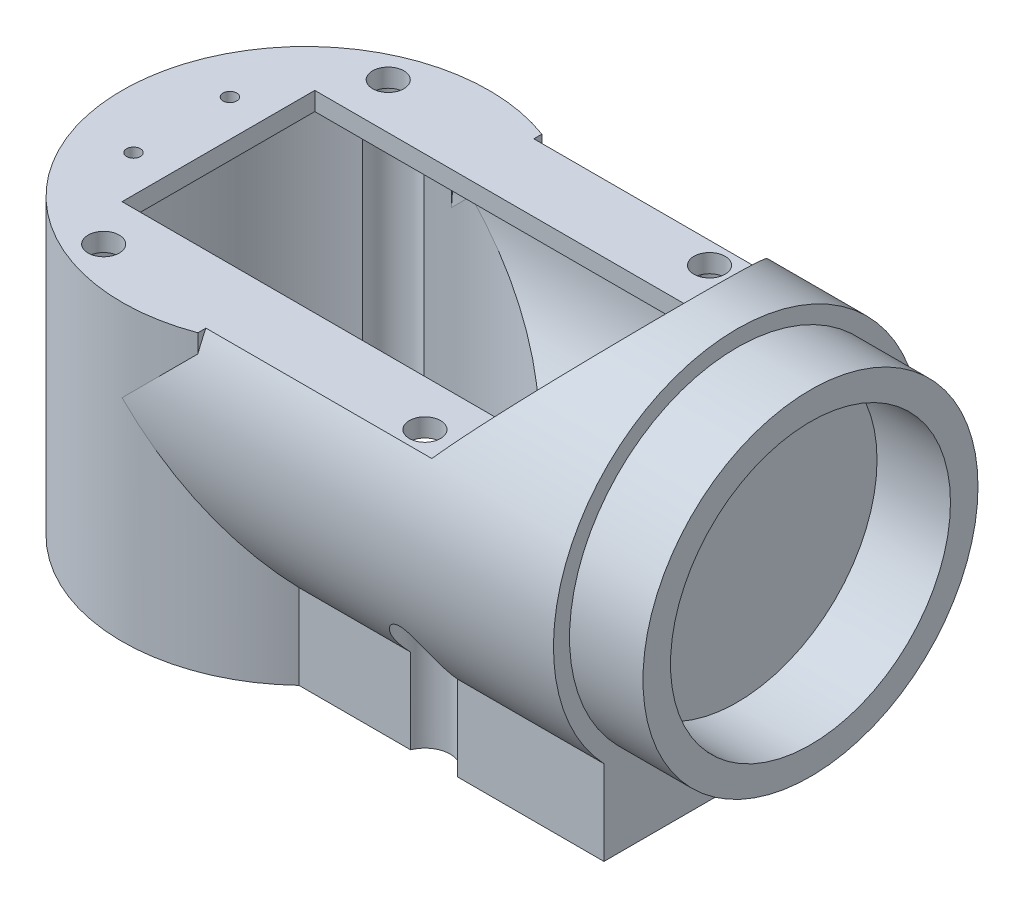
SolidWorks part; units mm, degrees
material "自定义塑料"
ref_plane "前视基准面" through (0, 0, 0) normal (0, 0, 1) x (1, 0, 0)
ref_plane "上视基准面" through (0, 0, 0) normal (0, 1, 0) x (1, 0, 0)
ref_plane "右视基准面" through (0, 0, 0) normal (1, 0, 0) x (0, 0, -1)
sketch "草图1" plane through (0, 0, 0) normal (0, 1, 0) x (1, 0, 0)
  line L1 (40, 12.5) -> (12.9518, 12.5)
  line L2 (40, -12.5) -> (12.9518, -12.5)
  line L4 (40, 14.5) -> (40, 12.5)
  line L5 (40, -12.5) -> (40, -14.5)
  line L7 (40, 14.5) -> (13.775, 14.5)
  line L8 (40, -14.5) -> (13.775, -14.5)
  arc A2 (12.9518, 12.5) -> (12.9518, -12.5) centre (0, 0) ccw
  arc A3 (13.775, 14.5) -> (13.775, -14.5) centre (0, 0) ccw
extrude "凸台-拉伸1" add sketch "草图1" along normal blind 30
sketch "草图6" plane through (40, 0, 0) normal (1, 0, 0) x (0, 0, -1)
  line L0 (-12.5, 30) -> (12.5, 30)
  line L1 (0, 30) -> (0, 23)
  circle A0 centre (0, 23) radius 20
  circle A1 centre (0, 23) radius 18
  line M2 (-12.5, 0) -> (-12.5, 30)
  line M4 (-14.5, 30) -> (-14.5, 0)
  dimension "D1" = 40
  dimension "D2" = 36
extrude "凸台-拉伸5" add sketch "草图6" against normal blind 40 contours A1 A0 M2 M4 | A1 A0 M4 M2 region at (40, 5.4821, -8.4153) region at (40, 9.7221, 13.5259)
sketch "草图11" plane through (40, 0, 0) normal (1, 0, 0) x (0, 0, -1)
  circle A0 centre (0, 23) radius 18
extrude "切除-拉伸2" cut sketch "草图11" against normal blind 42
sketch "草图10" plane through (0, 30, 0) normal (0, 1, 0) x (1, 0, 0)
  line L8 (40, 20.0595) -> (40, -20)
  line L9 (0, 20) -> (40, 20)
  line L11 (0, -20) -> (40, -20)
  line L12 (40, 20) -> (40, -20)
  arc A1 (0, 20) -> (0, -20) centre (0, 0) ccw
extrude "切除-拉伸3" cut sketch "草图10" along normal blind 20 contours L12 L9 A1 L11
sketch "草图13" plane through (0, 0, 0) normal (0, -1, 0) x (1, 0, 0)
  line L0 (0, 18) -> (0, -18) construction
  line L2 (40, -12.5) -> (12.9518, -12.5)
  line L3 (40, -12.5) -> (40, 12.5)
  line L4 (40, 12.5) -> (12.9518, 12.5)
  arc A0 (12.9518, 12.5) -> (12.9518, -12.5) centre (0, 0) ccw
extrude "切除-拉伸6" cut sketch "草图13" against normal blind 30
sketch "草图14" plane through (0, 30, 0) normal (0, 1, 0) x (1, 0, 0)
  line L1 (30, -18.735) -> (7, -18.735)
  line L3 (30, 18.735) -> (7, 18.735)
  line L4 (7, -10.5) -> (7, 10.5)
  line L5 (-9.5, -10.5) -> (31.5, -10.5)
  line L6 (-9.5, -10.5) -> (-9.5, 10.5)
  line L7 (-9.5, 10.5) -> (31.5, 10.5)
  line L18 (31.5, 10.5) -> (31.5, -10.5)
  line L20 (7, 16.5831) -> (40, 16.5831) construction
  line L21 (31.5, 16.5831) -> (40, 16.5831)
  line L22 (40, -16.5831) -> (31.5, -16.5831)
  line L23 (40, -16.5831) -> (7, -16.5831) construction
  line L25 (40, 16.5831) -> (40, -16.5831)
  line L26 (30, -16.5831) -> (30, -18.735)
  line L27 (30, 18.735) -> (30, 16.5831)
  line L28 (31.5, 16.5831) -> (30, 16.5831)
  line L29 (31.5, -16.5831) -> (30, -16.5831)
  circle A0 centre (-13.5, -5.25) radius 0.75
  circle A1 centre (-13.5, 5.25) radius 0.75
  circle A2 centre (35.5, 5.25) radius 0.75
  circle A3 centre (35.5, -5.25) radius 0.75
  arc A5 (7, 18.735) -> (7, -18.735) centre (0, 0) ccw
  line M6 (40, -16.5831) -> (7, -16.5831)
  arc M7 (7, -16.5831) -> (7, 16.5831) centre (0, 0) cw
  line M8 (7, 16.5831) -> (40, 16.5831)
  line M10 (40, 18.735) -> (7, 18.735)
  arc M11 (7, 18.735) -> (7, -18.735) centre (0, 0) ccw
  line M12 (7, -18.735) -> (40, -18.735)
  dimension "D3" = 4
  dimension "D1" = 41
  dimension "D2" = 21
  dimension "D4" = 5.25
  dimension "D5" = 10.5
  dimension "D6" = 10.5
sketch "草图15" plane through (40, 0, 0) normal (1, 0, 0) x (0, 0, -1)
  line L0 (12.5, 10.0482) -> (12.5, 7.3875)
  line L2 (-12.5, 7.3875) -> (-12.5, 10.0482)
  arc A0 (12.5, 7.3875) -> (-12.5, 7.3875) centre (0, 23) ccw
  arc A1 (12.5, 10.0482) -> (-12.5, 10.0482) centre (0, 23) ccw
extrude "凸台-拉伸7" add sketch "草图15" along normal blind 5 and the other way blind 10
extrude "凸台-拉伸9" add sketch "草图14" along normal blind 2 contours L27 L26 M10 M11 M12 M6 M7 M8 | L25 A1 A0 L7 L18 L5 L6 A2 A3 M8 M7 M6 region at (18.5, 30, 18.0947) region at (18.5, 30, 15.9005)
sketch "草图18" plane through (0, 32, 0) normal (0, 1, 0) x (1, 0, 0)
  circle A0 centre (20.85, 0) radius 20.85
extrude "切除-拉伸8" cut sketch "草图18" along normal blind 20
sketch "草图19" plane through (45, 0, 0) normal (1, 0, 0) x (0, 0, -1)
  line L0 (-17.8606, 32) -> (-18.735, 32)
  line L1 (18.735, 32) -> (17.8606, 32)
  line L2 (18.735, 32) -> (18.735, 30)
  line L4 (-18.735, 32) -> (-18.735, 30)
  arc A0 (-17.8606, 32) -> (-18.735, 30) centre (0, 23) ccw
  arc A2 (18.735, 30) -> (17.8606, 32) centre (0, 23) ccw
extrude "切除-拉伸10" cut sketch "草图19" against normal blind 38
sketch "草图20" plane through (40, 0, 0) normal (1, 0, 0) x (0, 0, -1)
  line L0 (-14.5, 9.225) -> (-14.5, 0)
  line L1 (-14.5, 0) -> (-12.5, 0)
  line L2 (-12.5, 0) -> (-12.5, 7.3875)
  line L4 (12.5, 7.3875) -> (12.5, 0)
  line L5 (12.5, 0) -> (14.5, 0)
  line L6 (14.5, 0) -> (14.5, 9.225)
  line L7 (-16.5831, 30) -> (16.5831, 30)
  line L8 (15.5885, 32) -> (-15.5885, 32)
  arc A0 (16.5831, 30) -> (15.5885, 32) centre (0, 23) ccw
  arc A1 (12.5, 7.3875) -> (14.5, 9.225) centre (0, 23) ccw
  arc A2 (-14.5, 9.225) -> (-12.5, 7.3875) centre (0, 23) ccw
  arc A3 (-15.5885, 32) -> (-16.5831, 30) centre (0, 23) ccw
extrude "凸台-拉伸10" add sketch "草图20" along normal blind 5
sketch "草图21" plane through (45, 0, 0) normal (1, 0, 0) x (0, 0, -1)
  line L1 (-14.5, 0) -> (14.5, 0)
  line L2 (-14.5, 0) -> (-14.5, 9.225)
  line L4 (14.5, 0) -> (14.5, 9.225)
  arc A0 (14.5, 9.225) -> (-14.5, 9.225) centre (0, 23) ccw
extrude "凸台-拉伸11" add sketch "草图21" along normal blind 2
sketch "草图22" plane through (47, 0, 0) normal (1, 0, 0) x (0, 0, -1)
  circle A0 centre (0, 23) radius 18.25
  circle A1 centre (0, 23) radius 15.25
  dimension "D1" = 36.5
  dimension "D2" = 30.5
extrude "凸台-拉伸13" add sketch "草图22" along normal blind 8
sketch "草图29" plane through (0, 0, 0) normal (0, -1, 0) x (1, 0, 0)
  line L1 (-9.5, -10.5) -> (31.5, -10.5)
  line L2 (-9.5, -10.5) -> (-9.5, 10.5)
  line L3 (-9.5, 10.5) -> (31.5, 10.5)
  line L4 (31.5, -10.5) -> (31.5, 10.5)
  line L5 (-9.5, -10.5) -> (31.5, -10.5)
  line L6 (-9.5, -10.5) -> (-9.5, -18.5)
  line L7 (-9.5, -18.5) -> (31.5, -18.5)
  line L8 (31.5, -10.5) -> (31.5, -18.5)
  circle A0 centre (-6.5, -15.5) radius 1.7
  circle A2 centre (28.5, -15.5) radius 1.7
  circle A3 centre (28.5, 15.5) radius 1.7
  circle A4 centre (-6.5, 15.5) radius 1.7
  arc M31 (12.9518, -12.5) -> (12.9518, 12.5) centre (0, 0) cw
  dimension "D1" = 3.4
  dimension "D2" = 3
  dimension "D3" = 3
  dimension "D4" = 2
extrude "切除-拉伸13" cut sketch "草图29" against normal through all contours A0 | A2 | A0 M31 | A4 | A2 | A3 region at (-6.4421, 0, -15.3619) region at (-7.0374, 0, -16.7815) region at (28.5, 0, -15.5)
sketch "草图30" plane through (0, 0, 0) normal (0, -1, 0) x (1, 0, 0)
  circle A0 centre (-6.5, -15.5) radius 2.75
  circle A1 centre (28.5, -15.5) radius 2.75
  circle A2 centre (28.5, 15.5) radius 2.75
  circle A3 centre (-6.5, 15.5) radius 2.75
  dimension "D1" = 2
extrude "切除-拉伸14" cut sketch "草图30" against normal blind 30
